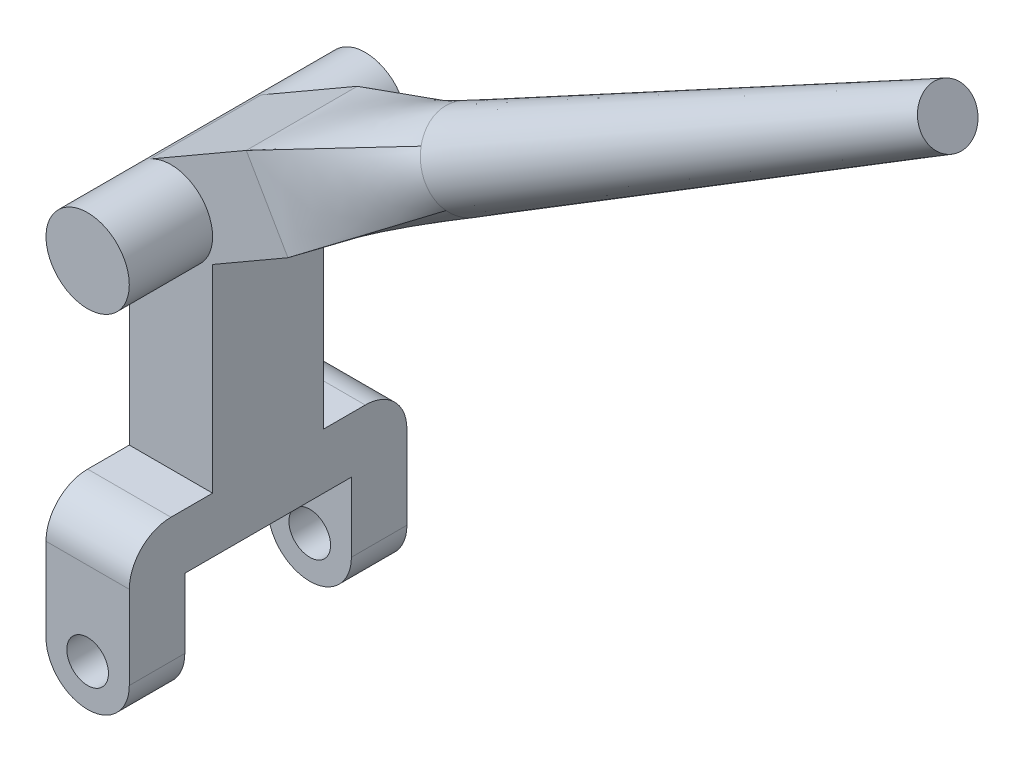
SolidWorks part; units mm, degrees
ref_plane "Front Plane" through (0, 0, 0) normal (0, 0, 1) x (1, 0, 0)
ref_plane "Top Plane" through (0, 0, 0) normal (0, 1, 0) x (1, 0, 0)
ref_plane "Right Plane" through (0, 0, 0) normal (1, 0, 0) x (0, 0, -1)
sketch "Sketch2" plane through (0, 0, 0) normal (0, 0, 1) x (1, 0, 0)
  circle A0 centre (0, 0) radius 9.525
  dimension "D1" = 19.05
extrude "Boss-Extrude1" add sketch "Sketch2" along normal blind 63.5
sketch "Sketch3" plane through (0, 0, 0) normal (0, 1, 0) x (1, 0, 0)
  line L0 (-9.525, 0) -> (-9.525, -63.5) construction
  line L1 (-9.525, -19.05) -> (9.525, -19.05)
  line L2 (-9.525, -19.05) -> (-9.525, -44.45)
  line L3 (-9.525, -44.45) -> (9.525, -44.45)
  line L4 (9.525, -19.05) -> (9.525, -44.45)
  line L5 (9.525, -63.5) -> (9.525, 0) construction
  line L6 (-9.525, 0) -> (-9.525, -63.5) construction
  point P9 (-9.525, -31.75)
  point P10 (-9.525, -31.75)
  dimension "D1" = 25.4
extrude "Boss-Extrude2" add sketch "Sketch3" against normal blind 50.8
ref_axis "Axis1" through (0, 0, 63.5) along (0, 0, -1)
ref_plane "Plane1" through (0, 0, 0) normal (0.866, 0.5, 0) x (0, 0, -1)
sketch "Sketch4" plane through (0, 0, 0) normal (0.866, 0.5, 0) x (0, 0, -1)
  line L0 (0, 9.525) -> (-63.5, 9.525) construction
  line L1 (-44.45, 9.525) -> (-19.05, 9.525)
  line L2 (-44.45, 9.525) -> (-44.45, -9.525)
  line L3 (-44.45, -9.525) -> (-19.05, -9.525)
  line L4 (-19.05, 9.525) -> (-19.05, -9.525)
  line L5 (-44.45, -48.7566) -> (-44.45, -4.7625) construction
extrude "Boss-Extrude3" add sketch "Sketch4" along normal blind 25.4
ref_plane "Plane2" through (54.9926, 31.75, 0) normal (0.866, 0.5, 0) x (0, 0, -1)
sketch "Sketch5" plane through (54.9926, 31.75, 0) normal (0.866, 0.5, 0) x (0, 0, -1)
  line L0 (-63.5, 0) -> (0, 0) construction
  line L1 (-19.05, 9.525) -> (-44.45, 9.525) construction
  circle A0 centre (-31.75, 0) radius 9.525
  point P7 (-31.75, 9.525)
sketch "Sketch6" plane through (21.997, 12.7, 0) normal (0.866, 0.5, 0) x (0, 0, -1)
  line L4 (-44.45, 9.525) -> (-44.45, -9.525)
  line L5 (-44.45, -9.525) -> (-19.05, -9.525)
  line L6 (-19.05, -9.525) -> (-19.05, 9.525)
  line L7 (-19.05, 9.525) -> (-44.45, 9.525)
  line L8 (-44.45, 9.525) -> (-44.45, -9.525)
  line L9 (-44.45, -9.525) -> (-19.05, -9.525)
  line L10 (-19.05, -9.525) -> (-19.05, 9.525)
  line L11 (-19.05, 9.525) -> (-44.45, 9.525)
  dimension "D1" = 0
loft "Loft1" add profiles "Sketch6", "Sketch5" connector at (17.2345, 20.9489, 44.45) connector at (53.2645, 34.7432, 40.6258)
extrude "Boss-Extrude4" add sketch "Sketch5<2>" along normal blind 127 draft 1.5
sketch "Sketch5<2>" plane through (54.9926, 31.75, 0) normal (0.866, 0.5, 0) x (0, 0, -1) same geometry as "Sketch5"
sketch "Sketch8" plane through (0, -50.8, 0) normal (0, -1, 0) x (1, 0, 0)
  line L1 (-9.525, 63.5) -> (9.525, 63.5)
  line L2 (-9.525, 63.5) -> (-9.525, 0)
  line L3 (-9.525, 0) -> (9.525, 0)
  line L4 (9.525, 63.5) -> (9.525, 0)
extrude "Boss-Extrude5" add sketch "Sketch8" along normal blind 12.7
sketch "Sketch9" plane through (0, -63.5, 0) normal (0, -1, 0) x (1, 0, 0)
  line L0 (9.525, 0) -> (9.525, 63.5) construction
  line L1 (-9.525, 63.5) -> (9.525, 63.5)
  line L2 (-9.525, 63.5) -> (-9.525, 50.8)
  line L3 (-9.525, 50.8) -> (9.525, 50.8)
  line L4 (9.525, 63.5) -> (9.525, 50.8)
  line L5 (-9.525, 63.5) -> (-9.525, 0) construction
  line L6 (9.525, 0) -> (-9.525, 0)
  line L7 (9.525, 0) -> (9.525, 12.7)
  line L8 (9.525, 12.7) -> (-9.525, 12.7)
  line L9 (-9.525, 0) -> (-9.525, 12.7)
  dimension "D1" = 12.7
extrude "Boss-Extrude6" add sketch "Sketch9" along normal blind 25.4
fillet "Fillet2" radius 9.525 4 edges at (9.525, -88.9, 6.35) (9.525, -88.9, 57.15) (-9.525, -88.9, 57.15) (-9.525, -88.9, 6.35)
sketch "Sketch12" plane through (0, 0, 0) normal (0, 0, -1) x (-1, 0, 0)
  circle A0 centre (0, -79.375) radius 4.7625
  arc A1 (0, -88.9) -> (9.525, -79.375) centre (0, -79.375) ccw construction
  dimension "D1" = 9.525
extrude "Cut-Extrude1" cut sketch "Sketch12" against normal through all
fillet "Fillet3" radius 9.525 2 edges at (0, -50.8, 63.5) (0, -50.8, 0)
